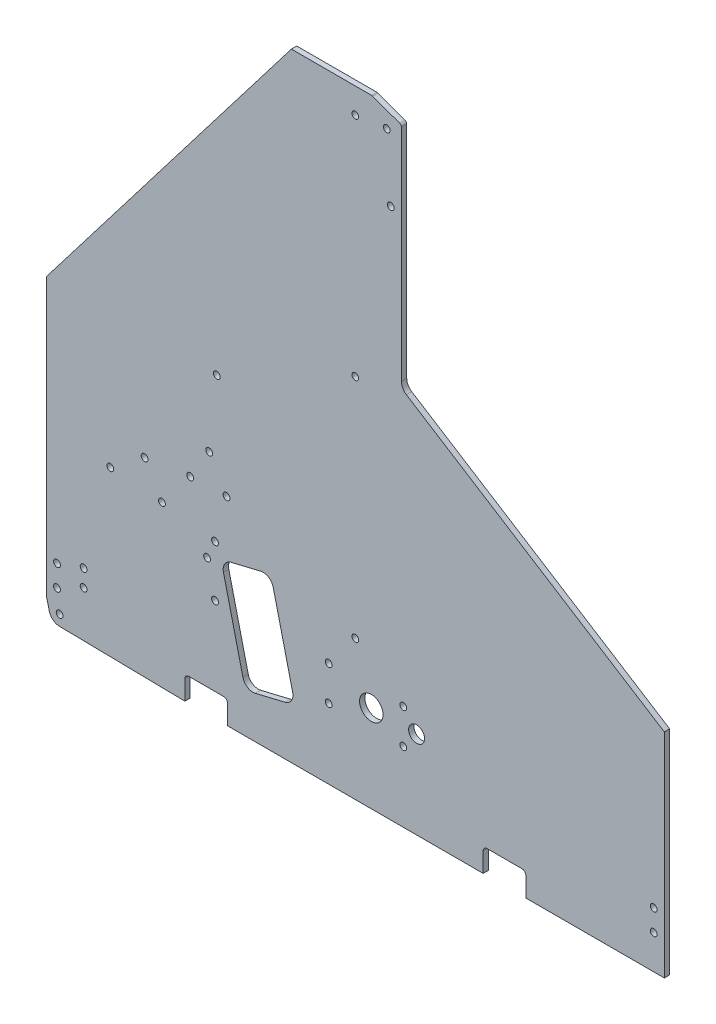
SolidWorks part; units mm, degrees
ref_plane "Front Plane" through (0, 0, 0) normal (0, 0, 1) x (1, 0, 0)
ref_plane "Top Plane" through (0, 0, 0) normal (0, 1, 0) x (1, 0, 0)
ref_plane "Right Plane" through (0, 0, 0) normal (1, 0, 0) x (0, 0, -1)
sketch "Sketch1" plane through (0, 0, 0) normal (0, 0, 1) x (1, 0, 0)
  line L0 (82.55, -20.32) -> (82.55, -6.35)
  line L2 (0, 0) -> (0, 157.48)
  line L4 (368.3, -20.32) -> (368.3, 106.68)
  line L5 (82.55, -6.35) -> (107.95, -6.35)
  line L6 (107.95, -6.35) -> (107.95, -20.32)
  line L7 (107.95, -20.32) -> (260.35, -20.32)
  line L8 (260.35, -20.32) -> (260.35, -6.35)
  line L9 (260.35, -6.35) -> (285.75, -6.35)
  line L10 (285.75, -6.35) -> (285.75, -20.32)
  line L11 (285.75, -20.32) -> (368.3, -20.32)
  line L12 (361.95, 12.7) -> (368.3, 12.7) construction
  line L13 (0, 0) -> (6.35, 0) construction
  line L14 (0.1896, -7.8901) -> (1.7771, -14.2401)
  line L15 (7.8295, -19.0491) -> (82.55, -20.32)
  line L16 (0, 0) -> (0, -6.35)
  line L17 (85.725, 97.155) -> (82.9754, 95.5675) construction
  line L18 (97.0634, 115.6163) -> (58.5686, 93.3913) construction
  line L19 (97.0634, 115.6163) -> (107.3822, 97.7437) construction
  line L20 (58.5686, 93.3913) -> (68.8873, 75.5187) construction
  line L21 (107.3822, 97.7437) -> (68.8873, 75.5187) construction
  line L22 (97.0634, 115.6163) -> (68.8873, 75.5187) construction
  line L23 (58.5686, 93.3913) -> (107.3822, 97.7437) construction
  line L24 (7.9375, -12.7) -> (95.7973, 60.4105) construction
  line L25 (184.15, 62.98) -> (184.15, 197.98) construction
  line L26 (184.15, 197.98) -> (184.15, 332.98) construction
  line L27 (355.6, 335.28) -> (330.2, 335.28) construction
  line L28 (330.2, 335.28) -> (330.2, 220.98) construction
  line L29 (330.2, 220.98) -> (355.6, 220.98) construction
  line L30 (355.6, 220.98) -> (355.6, 335.28) construction
  line L31 (184.15, 347.98) -> (184.15, 269.4703) construction
  line L32 (12.7, 335.28) -> (38.1, 335.28) construction
  line L33 (38.1, 335.28) -> (38.1, 220.98) construction
  line L34 (12.7, 220.98) -> (12.7, 335.28) construction
  line L35 (38.1, 220.98) -> (12.7, 220.98) construction
  line L36 (194.15, 347.98) -> (211.6138, 341.63)
  line L37 (184.15, 347.98) -> (146.05, 347.98)
  line L38 (184.15, 347.98) -> (194.15, 347.98)
  line L39 (348.5362, 347.98) -> (413.4623, 347.98)
  line L40 (348.5362, 347.98) -> (211.6138, 347.98) construction
  line L42 (146.05, 347.98) -> (0, 157.48)
  line L44 (211.6138, 341.63) -> (211.6138, 205.74)
  line L45 (211.6138, 205.74) -> (368.3, 106.68)
  line L46 (194.15, 347.98) -> (-141.0713, 347.98) construction
  circle A0 centre (6.35, 0) radius 2.032
  circle A1 centre (6.35, 12.7) radius 2.032
  circle A2 centre (361.95, 0) radius 2.032
  circle A3 centre (361.95, 12.7) radius 2.032
  arc A5 (1.7771, -14.2401) -> (7.8295, -19.0491) centre (7.9375, -12.7) ccw
  circle A6 centre (7.9375, -12.7) radius 2.032
  arc A7 (0, -6.35) -> (0.1896, -7.8901) centre (6.35, -6.35) ccw
  circle A8 centre (38.1, 78.105) radius 2.032
  circle A9 centre (85.725, 97.155) radius 2.032
  circle A10 centre (58.5686, 93.3913) radius 2.032
  circle A11 centre (68.8873, 75.5187) radius 2.032
  circle A12 centre (107.3822, 97.7437) radius 2.032
  circle A13 centre (97.0634, 115.6163) radius 2.032
  circle A14 centre (95.7973, 60.4105) radius 2.032
  circle A15 centre (184.15, 62.98) radius 2
  circle A16 centre (184.15, 197.98) radius 2
  circle A17 centre (184.15, 332.98) radius 2
  circle A18 centre (63.5, 316.23) radius 2.032
  circle A19 centre (101.6, 157.48) radius 2.032
  circle A20 centre (355.6, 335.28) radius 2.032
  circle A21 centre (330.2, 335.28) radius 2.032
  circle A22 centre (355.6, 220.98) radius 2.032
  circle A23 centre (330.2, 220.98) radius 2.032
  circle A24 centre (12.7, 335.28) radius 2.032
  circle A25 centre (38.1, 335.28) radius 2.032
  circle A26 centre (12.7, 220.98) radius 2.032
  circle A27 centre (38.1, 220.98) radius 2.032
  circle A28 centre (202.8819, 335.28) radius 2
  circle A29 centre (205.2638, 296.418) radius 2.032
  point P82 (184.15, 347.98)
  point P83 (202.8819, 344.805)
  dimension "D6" = 4.064
  dimension "D10" = 6.35
  dimension "D11" = 4.064
  dimension "D17" = 38.1
  dimension "D27" = 4
  dimension "D31" = 4.064
  dimension "D32" = 38.1
  dimension "D36" = 4.064
  dimension "D47" = 45.212
  dimension "D48" = 4.064
  dimension "D2" = 127
  dimension "D3" = 13.97
  dimension "D4" = 25.4
  dimension "D5" = 152.4
  dimension "D7" = 12.7
  dimension "D8" = 6.35
  dimension "D9" = 20.32
  dimension "D12" = 12.7
  dimension "D13" = 1.5875
  dimension "D14" = 82.55
  dimension "D15" = 368.3
  dimension "D16" = 6.35
  dimension "D18" = 98.425
  dimension "D19" = 47.625
  dimension "D20" = 19.05
  dimension "D21" = 3.175
  dimension "D22" = 60
  dimension "D23" = 20.6375
  dimension "D24" = 44.45
  dimension "D25" = 38.1
  dimension "D26" = 114.3
  dimension "D28" = 135
  dimension "D29" = 12.7
  dimension "D30" = 15
  dimension "D33" = 63.5
  dimension "D34" = 27.4638
  dimension "D35" = 101.6
  dimension "D37" = 114.3
  dimension "D38" = 25.4
  dimension "D39" = 12.7
  dimension "D40" = 157.48
  dimension "D41" = 142.24
  dimension "D42" = 368.3
  dimension "D43" = 10
  dimension "D44" = 6.35
  dimension "D45" = 31.75
  dimension "D46" = 6.35
  dimension "D49" = 6.35
extrude "Boss-Extrude1" add sketch "Sketch1" along normal blind 3.175 contours L16 A7 L14 A5 L15 L2 A0 A1 A6 region at (167.8922, 118.3155, 0)
fillet "Fillet1" radius 2.286 4 edges at (285.75, -6.35, 1.5875) (107.95, -6.35, 1.5875) (260.35, -6.35, 1.5875) (82.55, -6.35, 1.5875)
fillet "Fillet2" radius 6.35 1 edges at (211.6138, 205.74, 1.5875)
sketch "Sketch2" plane through (0, 0, 0) normal (0, 0, -1) x (-1, 0, 0)
  circle A0 centre (-100.5528, 71.086) radius 2.032 construction
  circle A1 centre (-100.5528, 40.606) radius 2.032 construction
  circle A2 centre (-22.225, 18.2025) radius 2.032 construction
  circle A3 centre (-22.225, 8.0425) radius 2.032 construction
  circle A4 centre (-100.5528, 71.086) radius 2.032
  circle A5 centre (-100.5528, 40.606) radius 2.032
  circle A6 centre (-22.225, 18.2025) radius 2.032
  circle A7 centre (-22.225, 8.0425) radius 2.032
extrude "Cut-Extrude1" cut sketch "Sketch2" against normal through all
fillet "Fillet3" radius 1.5875 2 edges at (211.6138, 341.63, 1.5875) (194.15, 347.98, 1.5875)
sketch "Sketch3" plane through (0, 0, 3.175) normal (0, 0, 1) x (1, 0, 0)
  line L0 (132.9524, 63.2646) -> (132.7215, 64.2281) construction
  line L1 (128.3814, 66.8897) -> (110.6828, 62.6472) construction
  line L2 (114.5132, 58.4237) -> (126.8822, 61.3887) construction
  line L3 (108.0212, 58.3071) -> (108.2522, 57.3436) construction
  line L4 (131.2006, 57.703) -> (140.0164, 20.9265) construction
  line L5 (144.0993, 16.7636) -> (132.9524, 63.2646) construction
  line L6 (108.2522, 57.3436) -> (119.3991, 10.8426) construction
  line L7 (121.1509, 16.4042) -> (112.3351, 53.1807) construction
  line L8 (119.3991, 10.8426) -> (119.6301, 9.8791) construction
  line L9 (144.3303, 15.8001) -> (144.0993, 16.7636) construction
  line L10 (137.8383, 15.6835) -> (125.4694, 12.7185) construction
  line L11 (123.9701, 7.2175) -> (141.6687, 11.4601) construction
  line L12 (132.9524, 63.2646) -> (132.7215, 64.2281)
  line L13 (128.3814, 66.8897) -> (110.6828, 62.6472)
  line L14 (114.5132, 58.4237) -> (126.8822, 61.3887)
  line L15 (108.0212, 58.3071) -> (108.2522, 57.3436)
  line L16 (131.2006, 57.703) -> (140.0164, 20.9265)
  line L17 (144.0993, 16.7636) -> (132.9524, 63.2646)
  line L18 (108.2522, 57.3436) -> (119.3991, 10.8426)
  line L19 (121.1509, 16.4042) -> (112.3351, 53.1807)
  line L20 (119.3991, 10.8426) -> (119.6301, 9.8791)
  line L21 (144.3303, 15.8001) -> (144.0993, 16.7636)
  line L22 (137.8383, 15.6835) -> (125.4694, 12.7185)
  line L23 (123.9701, 7.2175) -> (141.6687, 11.4601)
  line L24 (127.7894, 69.3598) -> (110.0908, 65.1172)
  line L25 (105.5512, 57.715) -> (105.7822, 56.7515)
  line L26 (105.7822, 56.7515) -> (116.9291, 10.2505)
  line L27 (116.9291, 10.2505) -> (117.16, 9.287)
  line L28 (124.5622, 4.7475) -> (142.2608, 8.99)
  line L29 (146.8003, 16.3922) -> (146.5694, 17.3557)
  line L30 (146.5694, 17.3557) -> (135.4225, 63.8567)
  line L31 (135.4225, 63.8567) -> (135.1915, 64.8202)
  arc A0 (132.7215, 64.2281) -> (128.6308, 66.9403) centre (129.2206, 63.3889) ccw construction
  arc A1 (110.6828, 62.6472) -> (110.4377, 62.5791) centre (111.522, 59.1463) ccw construction
  arc A2 (128.6308, 66.9403) -> (128.3814, 66.8897) centre (129.2206, 63.3889) ccw construction
  arc A3 (110.4377, 62.5791) -> (108.0212, 58.3071) centre (111.522, 59.1463) ccw construction
  arc A4 (119.6301, 9.8791) -> (123.7207, 7.1669) centre (123.1309, 10.7183) ccw construction
  arc A5 (141.9139, 11.5281) -> (144.3303, 15.8001) centre (140.8295, 14.9609) ccw construction
  arc A6 (141.6687, 11.4601) -> (141.9139, 11.5281) centre (140.8295, 14.9609) ccw construction
  arc A7 (123.7207, 7.1669) -> (123.9701, 7.2175) centre (123.1309, 10.7183) ccw construction
  arc A8 (132.7215, 64.2281) -> (128.6308, 66.9403) centre (129.2206, 63.3889) ccw
  arc A9 (110.6828, 62.6472) -> (110.4377, 62.5791) centre (111.522, 59.1463) ccw
  arc A10 (128.6308, 66.9403) -> (128.3814, 66.8897) centre (129.2206, 63.3889) ccw
  arc A11 (110.4377, 62.5791) -> (108.0212, 58.3071) centre (111.522, 59.1463) ccw
  arc A12 (119.6301, 9.8791) -> (123.7207, 7.1669) centre (123.1309, 10.7183) ccw
  arc A13 (141.9139, 11.5281) -> (144.3303, 15.8001) centre (140.8295, 14.9609) ccw
  arc A14 (141.6687, 11.4601) -> (141.9139, 11.5281) centre (140.8295, 14.9609) ccw
  arc A15 (123.7207, 7.1669) -> (123.9701, 7.2175) centre (123.1309, 10.7183) ccw
  arc A16 (110.0908, 65.1172) -> (109.6726, 65.0012) centre (111.522, 59.1463) ccw
  arc A17 (109.6726, 65.0012) -> (105.5512, 57.715) centre (111.522, 59.1463) ccw
  arc A18 (117.16, 9.287) -> (124.1369, 4.6613) centre (123.1309, 10.7183) ccw
  arc A19 (124.1369, 4.6613) -> (124.5622, 4.7475) centre (123.1309, 10.7183) ccw
  arc A20 (142.2608, 8.99) -> (142.6789, 9.1061) centre (140.8295, 14.9609) ccw
  arc A21 (142.6789, 9.1061) -> (146.8003, 16.3922) centre (140.8295, 14.9609) ccw
  arc A22 (135.1915, 64.8202) -> (128.2147, 69.446) centre (129.2206, 63.3889) ccw
  arc A23 (128.2147, 69.446) -> (127.7894, 69.3598) centre (129.2206, 63.3889) ccw
  ellipse E0 centre (124.5974, 48.8487) end of major axis (128.5376, 61.3578) minor radius 6 (131.2006, 57.703) -> (126.8822, 61.3887) ccw construction
  ellipse E1 centre (122.2349, 48.2824) end of major axis (113.0518, 57.6456) minor radius 6 (114.5132, 58.4237) -> (112.3351, 53.1807) ccw construction
  ellipse E2 centre (127.7541, 25.2585) end of major axis (131.6942, 37.7675) minor radius 6 (121.1509, 16.4042) -> (125.4694, 12.7185) ccw construction
  ellipse E3 centre (130.1166, 25.8248) end of major axis (139.2998, 16.4616) minor radius 6 (137.8383, 15.6835) -> (140.0164, 20.9265) ccw construction
  ellipse E4 centre (124.5974, 48.8487) end of major axis (120.6573, 36.3397) minor radius 6 (131.2006, 57.703) -> (126.8822, 61.3887) ccw
  ellipse E5 centre (122.2349, 48.2824) end of major axis (131.4181, 38.9192) minor radius 6 (114.5132, 58.4237) -> (112.3351, 53.1807) ccw
  ellipse E6 centre (127.7541, 25.2585) end of major axis (131.6942, 37.7675) minor radius 6 (121.1509, 16.4042) -> (125.4694, 12.7185) ccw
  ellipse E7 centre (130.1166, 25.8248) end of major axis (139.2998, 16.4616) minor radius 6 (137.8383, 15.6835) -> (140.0164, 20.9265) ccw
  dimension "D1" = 2.54
extrude "Cut-Extrude2" cut sketch "Sketch3" against normal through all contours A22 A23 L24 A16 A17 L25 L26 L27 A18 A19 L28 A20 A21 L29 L30 L31 A15 A12 L20 L18 L15 A11 A9 L13 A10 A8 L12 L17 L21 A13 A14 L23 | A12 A15 L23 A14 A13 L21 L17 L12 A8 A10 L13 A9 A11 L15 L18 L20 E7 L22 E6 L19 E5 L14 E4 L16 | L22 E7 L16 E4 L14 E5 L19 E6 region at (137.844, 39.8506, 3.175) region at (126.1758, 37.0536, 3.175) region at (128.1544, 68.6507, 3.175)
sketch "Sketch4" plane through (0, 0, 3.175) normal (0, 0, 1) x (1, 0, 0)
  line L0 (107.3822, 97.7437) -> (68.8873, 75.5187) construction
  line L1 (168.275, 21.4312) -> (212.725, 21.4312) construction
  line L2 (168.275, 21.4312) -> (168.275, 42.0687) construction
  line L3 (168.275, 42.0687) -> (212.725, 42.0687) construction
  line L4 (212.725, 21.4312) -> (212.725, 42.0687) construction
  line L5 (168.275, 21.4312) -> (212.725, 42.0687) construction
  line L6 (168.275, 42.0687) -> (212.725, 21.4312) construction
  line L7 (97.0634, 115.6163) -> (107.3822, 97.7437) construction
  line L8 (107.95, -20.32) -> (260.35, -20.32) construction
  line L10 (190.5, 31.75) -> (193.675, 31.75) construction
  line L11 (6.35, 12.7) -> (361.95, 12.7) construction
  line L12 (107.95, -6.35) -> (107.95, -20.32) construction
  line L13 (193.675, 31.75) -> (220.6625, 31.75) construction
  line L15 (194.15, 47.98) -> (174.15, 47.98) construction
  line L16 (194.15, 47.98) -> (194.15, 347.98) construction
  line L17 (194.15, 347.98) -> (174.15, 347.98) construction
  line L18 (174.15, 47.98) -> (174.15, 347.98) construction
  line L19 (194.15, 47.98) -> (174.15, 347.98) construction
  line L20 (194.15, 347.98) -> (174.15, 47.98) construction
  circle A0 centre (168.275, 42.0687) radius 2.032
  circle A1 centre (212.725, 42.0687) radius 2.032
  circle A2 centre (212.725, 21.4312) radius 2.032
  circle A3 centre (168.275, 21.4312) radius 2.032
  circle A4 centre (193.675, 31.75) radius 6.985
  circle A5 centre (220.6625, 31.75) radius 4.7625
  circle A7 centre (220.6625, 31.75) radius 14.2875 construction
  circle A8 centre (193.675, 31.75) radius 12.7 construction
  point P0 (190.5, 31.75)
  point P26 (184.15, 197.98)
  dimension "D1" = 4.064
  dimension "D4" = 13.97
  dimension "D7" = 9.525
  dimension "D10" = 25.4
  dimension "D11" = 28.575
  dimension "D2" = 52.07
  dimension "D3" = 3.175
  dimension "D5" = 82.55
  dimension "D6" = 26.9875
  dimension "D8" = 20
  dimension "D9" = 300
extrude "Cut-Extrude3" cut sketch "Sketch4" against normal through all
